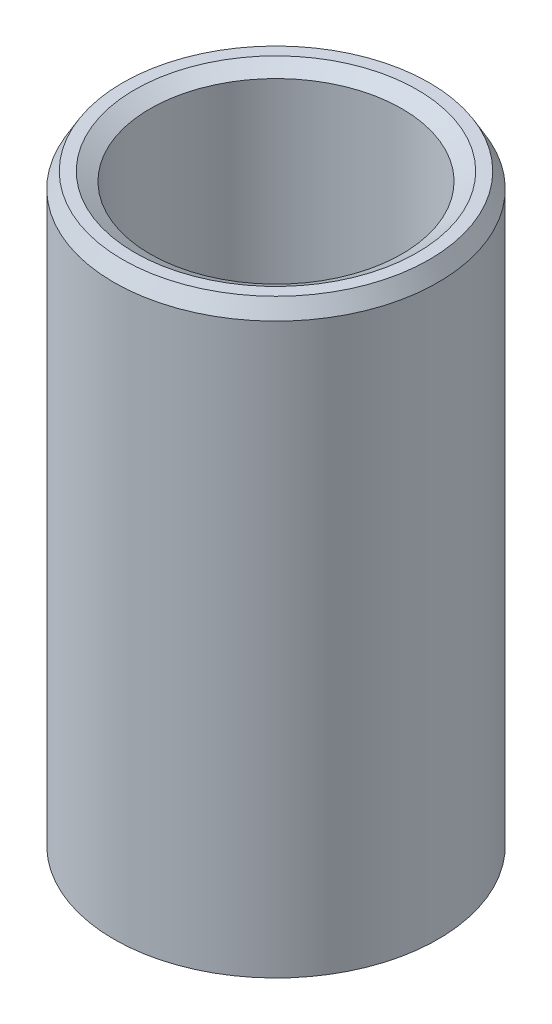
SolidWorks part; units mm, degrees
ref_plane "Front Plane" through (0, 0, 0) normal (0, 0, 1) x (1, 0, 0)
ref_plane "Top Plane" through (0, 0, 0) normal (0, 1, 0) x (1, 0, 0)
ref_plane "Right Plane" through (0, 0, 0) normal (1, 0, 0) x (0, 0, -1)
sketch "Sketch1" plane through (0, 0, 0) normal (0, 1, 0) x (1, 0, 0)
  circle A0 centre (0, 0) radius 15
  dimension "SLEEVE_OD" = 30
extrude "Boss-Extrude1" add sketch "Sketch1" along normal blind 54.8677
sketch "Sketch2" plane through (0, 0, 0) normal (0, 1, 0) x (1, 0, 0)
  circle A0 centre (0, 0) radius 11.6511
  dimension "BORE_D" = 23.3022
extrude "Cut-Extrude1" cut sketch "Sketch2" along normal through all
chamfer "Chamfer1" distance 1.4156 angle 30 4 edges at (0, 54.8677, 11.6511) (0, 0, 11.6511) (0, 0, 15) (0, 54.8677, 15) first distance on face at (0, 54.8677, 11.6511) first distance on face at (0, 0, 11.6511) first distance on face at (0, 54.8677, 15)
